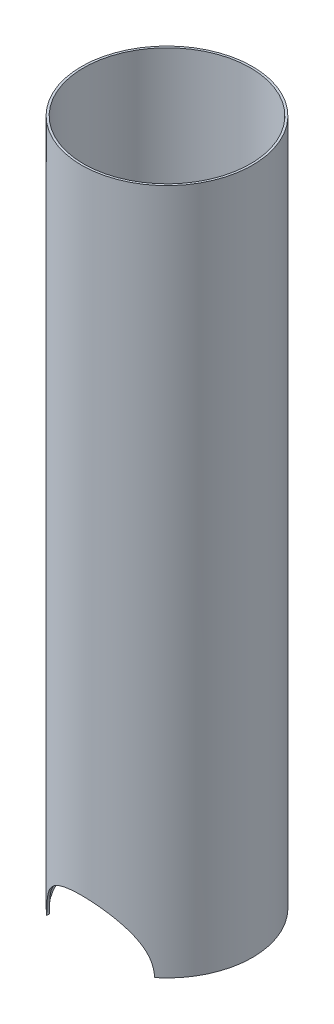
SolidWorks part; units mm, degrees
ref_plane "Front" through (0, 0, 0) normal (0, 0, 1) x (1, 0, 0)
ref_plane "Top" through (0, 0, 0) normal (0, 1, 0) x (1, 0, 0)
ref_plane "Right" through (0, 0, 0) normal (1, 0, 0) x (0, 0, -1)
ref_plane "Plane1" through (0, -110, 0) normal (0, 1, 0) x (1, 0, 0)
sketch "Sketch1" plane through (0, 0, 0) normal (0, 1, 0) x (1, 0, 0)
  circle A0 centre (0, 0) radius 63.5
  circle A1 centre (0, 0) radius 61.9125
  dimension "D1" = 127
  dimension "D2" = 1.5875
extrude "OEM" add sketch "Sketch1" along normal blind 457.2 and the other way blind 152.4
sketch "Sketch5" plane through (0, 0, 0) normal (0, 0, 1) x (1, 0, 0)
  line L0 (-63.5, -152.4) -> (63.5, -152.4) construction
  line L1 (-40, -152.4) -> (40, -152.4) construction
  arc A0 (40, -152.4) -> (-40, -152.4) centre (0, -152.4) ccw
  dimension "D1" = 40
extrude "eNSR baseplate cutout" cut sketch "Sketch5" against normal through all both and the other way through all
sketch "Sketch6" plane through (0, 0, 0) normal (0, 0, 1) x (1, 0, 0)
  line L0 (63.5, -152.4) -> (63.5, 457.2) construction
  line L1 (-63.5, 457.2) -> (63.5, 457.2)
  line L2 (-63.5, 457.2) -> (-63.5, 357.2)
  line L3 (-63.5, 357.2) -> (63.5, 357.2)
  line L4 (63.5, 457.2) -> (63.5, 357.2)
  dimension "D1" = 100
extrude "too long" cut sketch "Sketch6" against normal through all both and the other way through all
sketch "Sketch7" plane through (0, -110, 0) normal (0, 1, 0) x (1, 0, 0)
  circle A1 centre (58.7375, 0) radius 3.175
  circle A2 centre (58.7375, 0) radius 4.7625
  dimension "D1" = 6.35
  dimension "D2" = 1.5875
extrude "conduit" add sketch "Sketch7" along normal blind 300 and the other way blind 10
sketch "Sketch3" plane through (0, -110, 0) normal (0, 1, 0) x (1, 0, 0)
  circle A0 centre (0, 0) radius 63.5
  circle A1 centre (58.7375, 0) radius 3.175
  dimension "D1" = 127
extrude "floor" add sketch "Sketch3" along normal blind 1.5875
